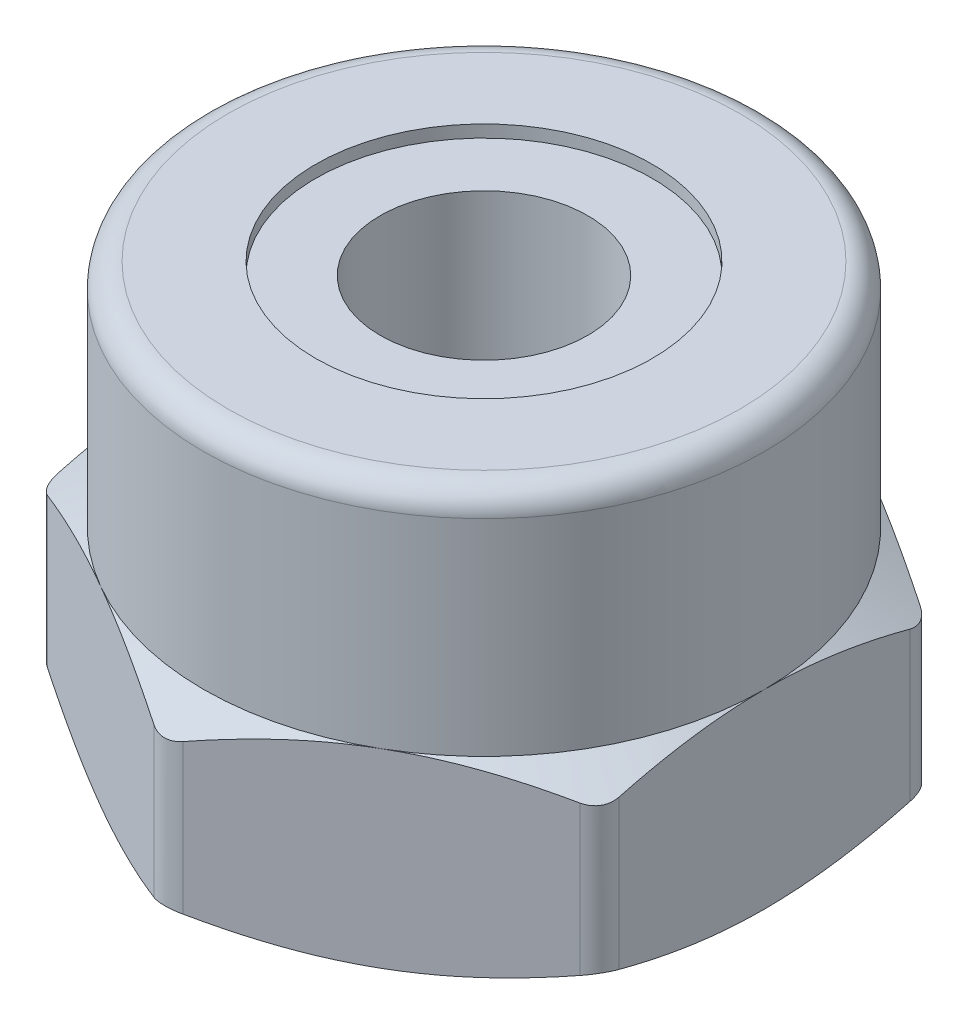
SolidWorks part; units mm, degrees
ref_plane "Front Plane" through (0, 0, 0) normal (0, 0, 1) x (1, 0, 0)
ref_plane "Top Plane" through (0, 0, 0) normal (0, 1, 0) x (1, 0, 0)
ref_plane "Right Plane" through (0, 0, 0) normal (1, 0, 0) x (0, 0, -1)
sketch "Sketch1" plane through (0, 0, 0) normal (0, 0, 1) x (1, 0, 0)
  line L0 (-2, -1.5) -> (2, -1.5) construction
  line L1 (-2, -1.5) -> (-2, -0.1433) construction
  line L2 (-2, -0.1433) -> (2, -0.1433) construction
  line L7 (2, -0.1433) -> (2, -1.5) construction
  line L8 (0, 1.5) -> (0, -1.5) construction
  line L9 (-1, 1.5) -> (-1, -1.5) construction
  line L10 (1, 1.5) -> (1, -1.5) construction
  line L11 (-1, 1.5) -> (1, 1.5) construction
  line L14 (2, -1.5) -> (2.3089, -1.3217) construction
  line L15 (2, -0.1433) -> (2, 1.5) construction
  line L16 (2, 1.5) -> (1, 1.5) construction
  line L17 (2.3089, -1.3217) -> (2.3089, -0.3217) construction
  line L18 (-2, -0.1433) -> (-2, 1.5) construction
  line L19 (-2, 1.5) -> (-1, 1.5) construction
  line L20 (2.3089, -0.3217) -> (2, -0.1433) construction
  line L21 (-1, -1.5) -> (-1, -1.85) construction
  line L22 (-1, -1.85) -> (-0.6969, -1.675) construction
  line L23 (-0.6969, -1.675) -> (-1, -1.5) construction
  line L24 (-1.0433, -1.475) -> (-1.0433, -1.875) construction
  line L25 (-1.0433, -1.475) -> (-1, -1.5) construction
  line L26 (-1, -1.85) -> (-1.0433, -1.875) construction
  line L27 (-0.7402, -1.65) -> (-0.7402, -1.7) construction
  line L28 (-1, -1.675) -> (-1.0433, -1.675) construction
  line L29 (-0.7402, -1.675) -> (-0.6969, -1.675) construction
  dimension "Width | s" = 4
  dimension "Thread Diameter" = 2
  dimension "Height | h" = 3
  dimension "D1" = 4.6178
  dimension "D2" = 30
  dimension "Flats Height" = 1
  dimension "Thread Pitch" = 0.4
  dimension "D4" = 0.05
sketch "Sketch2" plane through (0, 0, 0) normal (0, 1, 0) x (1, 0, 0)
  line L0 (0, 0) -> (1, 1.7321) construction
  line L1 (2, 1.1547) -> (0, 2.3094)
  line L2 (0, 2.3094) -> (-2, 1.1547)
  line L3 (-2, 1.1547) -> (-2, -1.1547)
  line L4 (-2, -1.1547) -> (0, -2.3094)
  line L5 (0, -2.3094) -> (2, -1.1547)
  line L6 (2, -1.1547) -> (2, 1.1547)
  line L7 (0, 0) -> (2, 1.1547) construction
  circle A0 centre (0, 0) radius 2 construction
  circle A1 centre (0, 0) radius 2.3094 construction
extrude "Boss-Extrude1" add sketch "Sketch2" against normal up to vertex (1.5 mm away) from vertex up to point (2, -1.5, 0) starting at point (2, -0.1433, 0)
sketch "Sketch3" plane through (0, 0, 0) normal (0, 0, 1) x (1, 0, 0)
  line L3 (1, 0.434) -> (2.3189, -0.3274)
  line L4 (1, 1.5) -> (1, -1.5) construction
  line L5 (1, -2.0774) -> (2.3189, -1.3159)
  line L6 (2.3189, -1.3159) -> (2.3189, -2.0774)
  line L7 (2.3189, -2.0774) -> (1, -2.0774)
  line L8 (1, 0.434) -> (2.3189, 0.434)
  line L10 (2.3189, -0.3274) -> (2.3189, 0.434)
  dimension "D1" = 0.01
revolve "Cut-Revolve1" cut sketch "Sketch3" angle 360 about L8
fillet "Fillet1" radius 0.2059 6 edges at (-2, -0.8217, -1.1547) (-2, -0.8217, 1.1547) (0, -0.8217, 2.3094) (0, -0.8217, -2.3094) (2, -0.8217, -1.1547) (2, -0.8217, 1.1547)
sketch "Sketch5" plane through (0, 0, 0) normal (0, 0, 1) x (1, 0, 0)
  line L0 (-1.2, -1.5) -> (-1, -1.3)
  line L1 (-2, -1.5) -> (2, -1.5) construction
  line L2 (-1, 1.5) -> (-1, -1.5) construction
  line L3 (-1, -1.3) -> (-1, -0.3433)
  line L4 (-1, -0.3433) -> (-1.2, -0.1433)
  line L5 (-2, -0.1433) -> (2, -0.1433) construction
  line L6 (-1.2, -0.1433) -> (0, -0.1433)
  line L7 (0, -0.1433) -> (0, -1.5)
  line L8 (0, -1.5) -> (-1.2, -1.5)
  line L9 (0, 1.5) -> (0, -1.5) construction
  dimension "D1" = 45
  dimension "D2" = 0.2
revolve "Cut-Revolve2" cut sketch "Sketch5" angle 360 about L8
sketch "Sketch4" plane through (0, 0, 0) normal (0, 0, 1) x (1, 0, 0)
  line L0 (-1.2, 1.5) -> (-1.825, 1.5)
  line L1 (-2, 1.5) -> (-1, 1.5) construction
  line L2 (-2, 1.325) -> (-2, -0.1433)
  line L4 (-1.825, 1.5) -> (-1.825, 1.325) construction
  line L5 (-0.8484, -1.5875) -> (-0.8484, -1.7625) construction
  line L6 (-0.6969, -1.675) -> (-1, -1.5) construction
  line L7 (-1, -1.85) -> (-0.6969, -1.675) construction
  line L8 (-2, -0.1433) -> (-1.9125, -0.1433)
  line L10 (-1.2, 1.4125) -> (-1.2, 1.5)
  line L11 (-1.2, 1.4125) -> (-1.825, 1.4125)
  line L12 (-1.9125, 1.325) -> (-1.9125, -0.1433)
  arc A0 (-2, 1.325) -> (-1.825, 1.5) centre (-1.825, 1.325) cw
  arc A1 (-1.825, 1.4125) -> (-1.9125, 1.325) centre (-1.825, 1.325) ccw
revolve "Revolve1" add sketch "Sketch4" angle 360 about L8
sketch "Sketch6" plane through (0, 0, 0) normal (0, 0, 1) x (1, 0, 0)
  line L0 (-2, -0.1433) -> (2, -0.1433) construction
  line L1 (-1.825, 1.4125) -> (-0.7402, 1.4125)
  line L2 (-1.9125, 1.325) -> (-1.9125, -0.1433)
  line L3 (-1.9125, -0.1433) -> (-0.7402, -0.1433)
  line L4 (-0.7402, 1.4125) -> (-0.7402, -0.1433)
  arc A0 (-1.825, 1.4125) -> (-1.9125, 1.325) centre (-1.825, 1.325) ccw
revolve "Revolve2" add sketch "Sketch6" angle 360 about L8
sketch "Sketch7" plane through (0, -1.5, 0) normal (0, 1, 0) x (-1, 0, 0)
  line L0 (1, 0) -> (-1, 0) construction
  line L1 (0, 0) -> (-0.7071, -0.7071) construction
  circle A0 centre (0, 0) radius 1
  point P7 (-0.7071, -0.7071)
  dimension "D1" = 225
curve "Helix/Spiral1" pitch 0.4 height 3 radius 1 left hand yes centre (0, -1.5, 0) axis (0, 1, 0) start towards (0, 0, 1)
sketch "Sketch8" plane through (0, 0, 0) normal (0, 0, 1) x (1, 0, 0)
  line L0 (-1.0217, -1.4875) -> (-1.0217, -1.8625)
  line L1 (-1.0433, -1.475) -> (-1, -1.5) construction
  line L2 (-1, -1.85) -> (-1.0433, -1.875) construction
  line L3 (-1.0217, -1.8625) -> (-0.7402, -1.7)
  line L4 (-0.7402, -1.7) -> (-0.7402, -1.65)
  line L5 (-0.7402, -1.65) -> (-1.0217, -1.4875)
sweep "Sweep1" add profiles "Sketch8" path "Helix/Spiral1"
sketch "Sketch9" plane through (0, 0, 0) normal (0, 0, 1) x (1, 0, 0)
  line L0 (-1.2, 1.5875) -> (-1.2, -0.1433)
  line L1 (-1.2, -0.1433) -> (-0.6969, -0.6464)
  line L2 (-0.6969, -0.6464) -> (-0.6969, 1.5875)
  line L4 (-0.6969, 1.5875) -> (-1.2, 1.5875)
  line L5 (-0.6969, -0.9969) -> (-1.2, -1.5)
  line L6 (-1.2, -1.5) -> (-1.2, -1.875)
  line L7 (-1.2, -1.875) -> (-0.6969, -1.875)
  line L8 (-0.6969, -1.875) -> (-0.6969, -0.9969)
  line L9 (-0.9484, 1.5875) -> (-0.9484, 1.5) construction
  line L10 (-1, 1.5) -> (1, 1.5) construction
  line L12 (-1.2, 1.4125) -> (-1.2, 1.5) construction
revolve "Cut-Revolve3" cut sketch "Sketch9" angle 360 about L8
equation "\"D1@Sketch1\"=\"Width | s@Sketch1\"*(1.15+.04/9)"
equation "\"D1@Fillet1\"=(\"D1@Sketch1\"-\"Width | s@Sketch1\")/3"
equation "\"D4@Sketch1\" = \"Thread Pitch@Sketch1\" / 8"
equation "\"D2@Sketch5\"=\"Thread Pitch@Sketch1\"*.5"
equation "\"D3@Helix/Spiral1\"=\"Height | h@Sketch1\""
equation "\"D4@Helix/Spiral1\"=\"Thread Pitch@Sketch1\""
